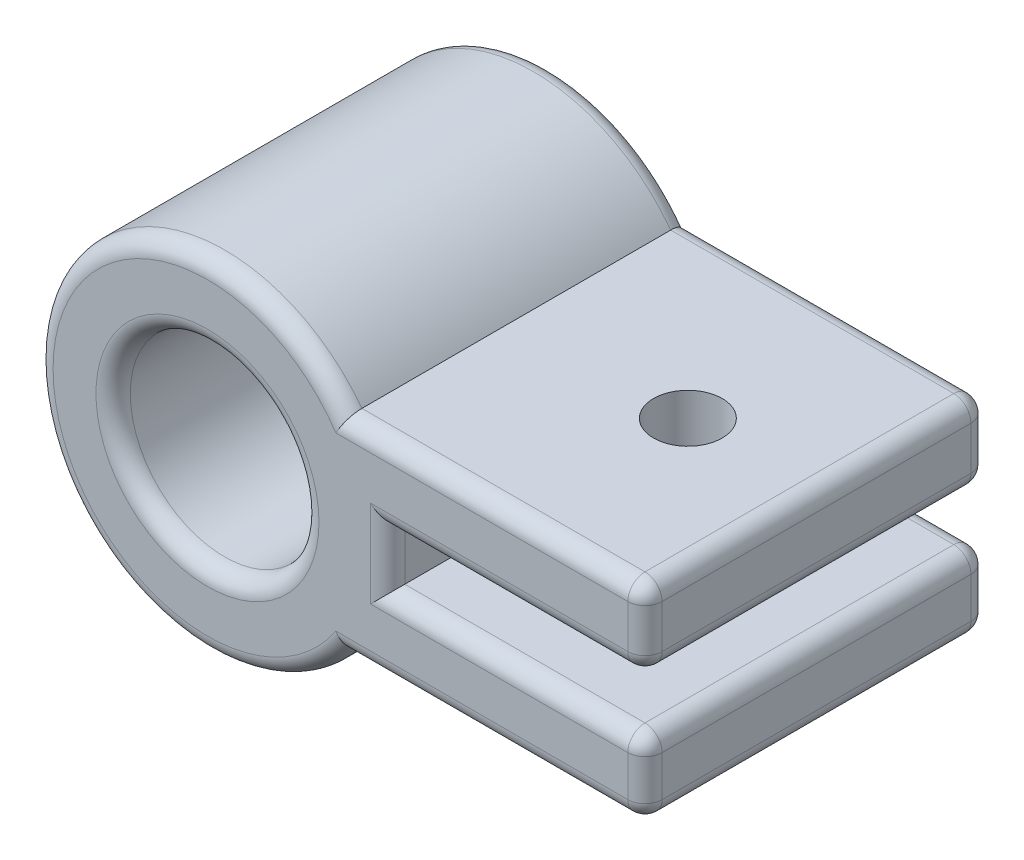
SolidWorks part; units mm, degrees
material "尼龙 101"
ref_plane "前视基准面" through (0, 0, 0) normal (0, 0, 1) x (1, 0, 0)
ref_plane "上视基准面" through (0, 0, 0) normal (0, 1, 0) x (1, 0, 0)
ref_plane "右视基准面" through (0, 0, 0) normal (1, 0, 0) x (0, 0, -1)
sketch "草图1" plane through (0, 0, 0) normal (0, 0, 1) x (1, 0, 0)
  circle A0 centre (0, 0) radius 10
  circle A1 centre (0, 0) radius 5.5
  dimension "D1" = 11
  dimension "D2" = 20
extrude "凸台-拉伸1" add sketch "草图1" along normal blind 20
sketch "草图2" plane through (0, 0, 0) normal (0, 1, 0) x (1, 0, 0)
  line L1 (5.5, 0) -> (25.5, 0)
  line L2 (5.5, 0) -> (5.5, -20)
  line L3 (5.5, -20) -> (25.5, -20)
  line L4 (25.5, 0) -> (25.5, -20)
  circle A0 centre (18, -10) radius 2
  point P8 (25.5, -10)
  dimension "D3" = 4
  dimension "D4" = 18
  dimension "D1" = 20
  dimension "D2" = 0
  dimension "D5" = 20
extrude "凸台-拉伸2" add sketch "草图2" along normal blind 6 and the other way blind 6
sketch "草图3" plane through (25.5, 0, 0) normal (1, 0, 0) x (0, 0, -1)
  line L0 (-20, -6) -> (-20, 6) construction
  line L1 (-20, 1.4729) -> (0, 1.4729)
  line L2 (-20, 1.4729) -> (-20, -1.6271)
  line L3 (-20, -1.6271) -> (0, -1.6271)
  line L4 (0, 1.4729) -> (0, -1.6271)
  line L5 (0, -6) -> (0, 6) construction
  dimension "D1" = 3.1
extrude "切除-拉伸1" cut sketch "草图3" against normal blind 15
fillet "圆角1" radius 1 22 edges at (25.5, -6, 10) (25.5, -1.6271, 10) (25.5, 6, 10) (25.5, 1.4729, 10) (5.5, 0, 0) (16.75, 6, 0) (-10, 0, 0) (16.75, -6, 0) (25.5, -3.8136, 0) (18, -1.6271, 0) (10.5, -0.0771, 0) (18, 1.4729, 0) (25.5, 3.7364, 0) (5.5, 0, 20) (10.5, -0.0771, 20) (18, -1.6271, 20) (25.5, -3.8136, 20) (16.75, -6, 20) (-10, 0, 20) (16.75, 6, 20) (25.5, 3.7364, 20) (18, 1.4729, 20)
